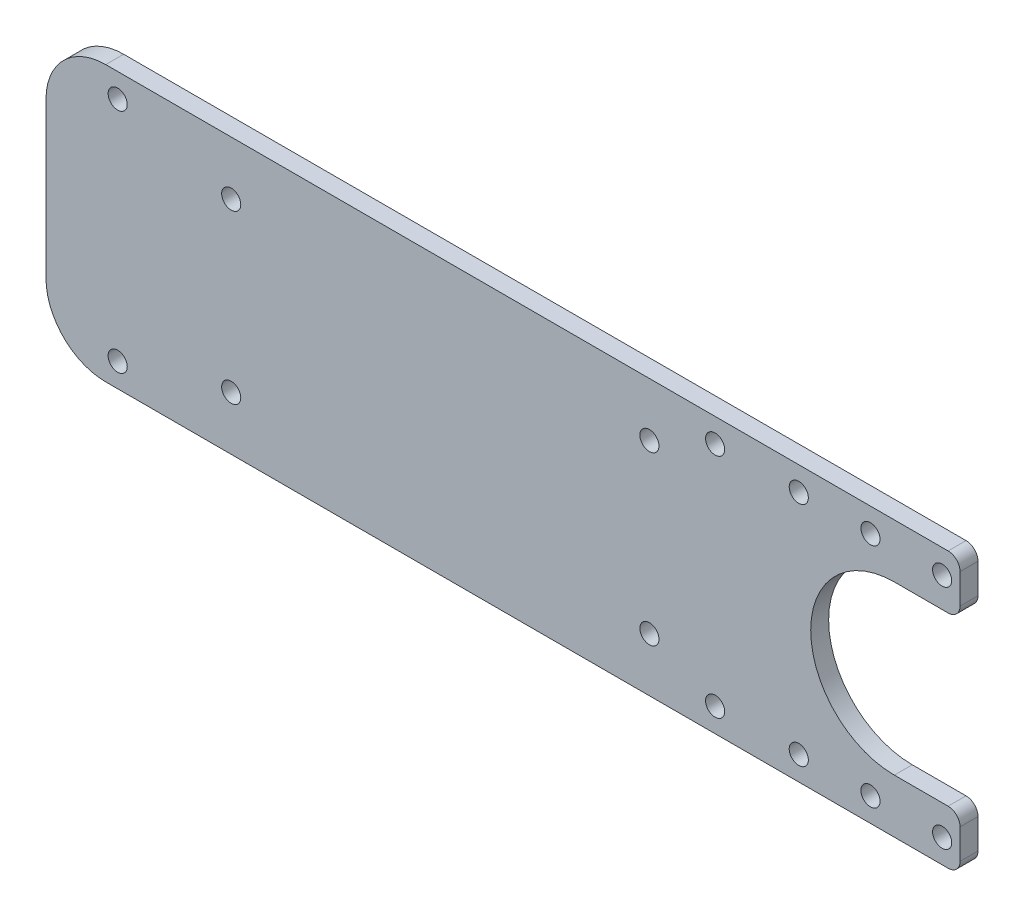
SolidWorks part; units mm, degrees
note: The reader was unsure of these and kept them because the rebuilt part matched: shared geometry of "Sketch3<3>".
material "Acrylic (Medium-high impact)"
ref_plane "Front Plane" through (0, 0, 0) normal (0, 0, 1) x (1, 0, 0)
ref_plane "Top Plane" through (0, 0, 0) normal (0, 1, 0) x (1, 0, 0)
ref_plane "Right Plane" through (0, 0, 0) normal (1, 0, 0) x (0, 0, -1)
sketch "Sketch2" plane through (0, 0, 0) normal (0, 0, 1) x (1, 0, 0)
  line L0 (56, 23) -> (56, 17)
  line L1 (56, -23) -> (-56, -23)
  line L2 (56, -23) -> (56, 23)
  line L3 (56, 23) -> (-56, 23)
  line L4 (-56, -23) -> (-56, 23)
  line L5 (56, -23) -> (-56, 23) construction
  line L6 (56, 23) -> (-56, -23) construction
  line L7 (56, 23) -> (86, 23)
  line L8 (56, 23) -> (56, -23)
  line L9 (56, -23) -> (86, -23)
  line L10 (86, 23) -> (86, -23)
  line L11 (0, 0) -> (10, 0)
  line L12 (56, -23) -> (56, -17)
  line L13 (10, 0) -> (10, -14)
  line L14 (10, -14) -> (45, -14)
  circle A0 centre (45, -14) radius 1.6
  circle A1 centre (-25, -14) radius 1.6
  circle A2 centre (45, 14) radius 1.6
  circle A3 centre (-25, 14) radius 1.6
  point P0 (0, 0)
  dimension "D7" = 3.2
  dimension "D1" = 112
  dimension "D2" = 46
  dimension "D3" = 30
  dimension "D4" = 10
  dimension "D5" = 35
  dimension "D6" = 14
extrude "Boss-Extrude1" add sketch "Sketch2" along normal blind 3
sketch "Sketch3" plane through (0, 0, 3) normal (0, 0, 1) x (1, 0, 0)
  line L0 (86, 23) -> (86, -23)
  line L1 (86, 23) -> (66, 23)
  line L2 (86, -23) -> (66, -23)
  line L3 (66, 23) -> (66, -23)
  line L4 (-56, 23) -> (-56, -23)
  line L5 (-56, -23) -> (86, -23)
  line L6 (86, -23) -> (86, 23)
  line L7 (-56, -23) -> (86, -23)
  line L8 (-56, 23) -> (-56, -23)
  line L10 (86, -23) -> (86, 23)
  line L12 (86, 23) -> (66, 23)
  line L13 (86, 19) -> (66, 19)
  line L14 (66, -19) -> (86, -19)
  line L15 (70, 23) -> (70, -19)
  line L17 (82, 23) -> (82, -23)
  line L18 (66, 0) -> (-44, 0)
  line L19 (-44, 0) -> (-44, 19)
  line L20 (-44, 19) -> (56, 19)
  line L21 (86, 14) -> (97, 14)
  line L22 (97, 14) -> (97, 23)
  line L23 (97, 23) -> (86, 23)
  line L24 (82, 19) -> (94, 19)
  line L25 (86, -14) -> (97, -14)
  line L26 (97, -23) -> (86, -23)
  line L27 (97, -14) -> (97, -23)
  line L28 (86, -19) -> (70, -19) construction
  line L29 (70, 23) -> (70, -19) construction
  line L33 (86, 23) -> (-56, 23)
  line L34 (86, 23) -> (-56, 23)
  circle A0 centre (70, 19) radius 1.6
  circle A1 centre (82, 19) radius 1.6
  circle A2 centre (82, -19) radius 1.6
  circle A3 centre (70, -19) radius 1.6
  circle A4 centre (-44, 19) radius 1.6
  circle A5 centre (56, 19) radius 1.6
  circle A6 centre (-44, -19) radius 1.6
  circle A7 centre (56, -19) radius 1.6
  circle A8 centre (86, 0) radius 14
  circle A9 centre (94, 19) radius 1.6
  circle A10 centre (94, -19) radius 1.6
  point P25 (82, 19)
  point P26 (-44, 9.5)
  point P27 (70, -19)
  dimension "D7" = 3.2
  dimension "D8" = 3.2
  dimension "D9" = 3.2
  dimension "D10" = 3.2
  dimension "D14" = 3.2
  dimension "D15" = 3.2
  dimension "D16" = 28
  dimension "D19" = 3.2
  dimension "D2" = 20
  dimension "D3" = 4
  dimension "D4" = 4
  dimension "D11" = 19
  dimension "D12" = 110
  dimension "D13" = 100
  dimension "D17" = 15
  dimension "D18" = 12
  dimension "D1" = 0
  dimension "D5" = 4
  dimension "D6" = 4
extrude "Cut-Extrude1" cut sketch "Sketch3" against normal through all
extrude "Boss-Extrude2" add sketch "Sketch3<3>" against normal up to surface (3 mm away)
sketch "Sketch3<3>" plane through (0, 0, 3) normal (0, 0, 1) x (1, 0, 0) same geometry as "Sketch3"
fillet "Fillet2" radius 2 2 edges at (97, 23, 1.5) (97, -23, 1.5)
fillet "Fillet3" radius 2 2 edges at (97, -14, 1.5) (97, 14, 1.5)
fillet "Fillet4" radius 10 2 edges at (-56, -23, 1.5) (-56, 23, 1.5)
